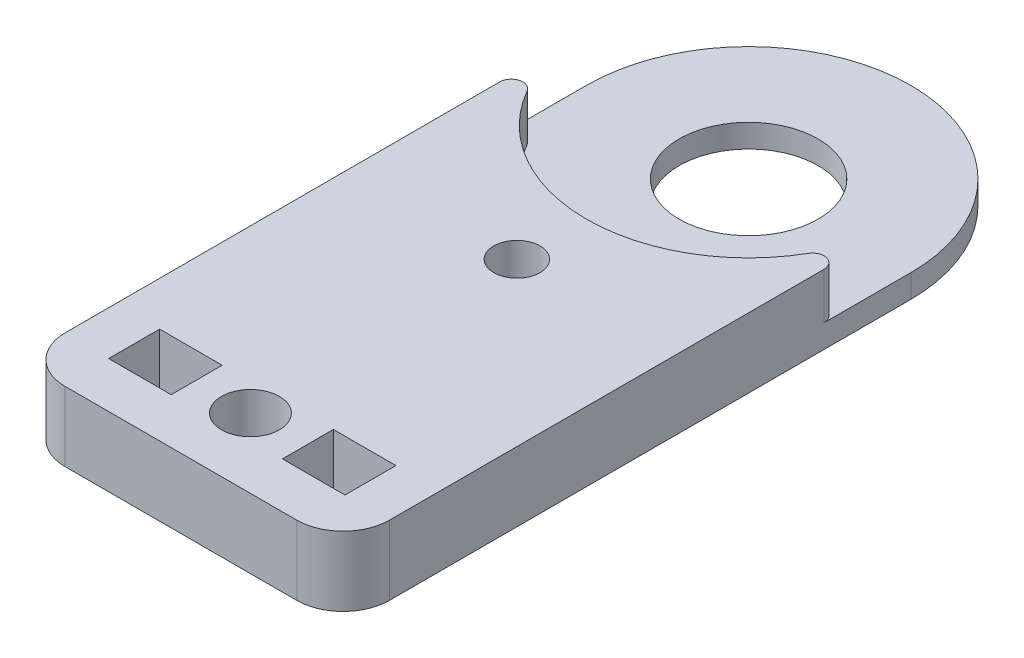
SolidWorks part; units mm, degrees
note: The reader was unsure of these and kept them because the rebuilt part matched: shared geometry of "草图1<4>".
ref_plane "前视基准面" through (0, 0, 0) normal (0, 0, 1) x (1, 0, 0)
ref_plane "上视基准面" through (0, 0, 0) normal (0, 1, 0) x (1, 0, 0)
ref_plane "右视基准面" through (0, 0, 0) normal (1, 0, 0) x (0, 0, -1)
sketch "草图1" plane through (0, 0, 0) normal (0, 1, 0) x (1, 0, 0)
  line L0 (0, 12.25) -> (0, 2.25)
  line L1 (-7, -12.25) -> (7, -12.25)
  line L2 (-7, -12.25) -> (-7, 12.25)
  line L3 (-7, 12.25) -> (7, 12.25)
  line L4 (7, -12.25) -> (7, 12.25)
  line L5 (-7, -12.25) -> (7, 12.25) construction
  line L6 (-7, 12.25) -> (7, -12.25) construction
  line L7 (0, 0) -> (0, -12.25) construction
  line L8 (-2.4, -8.0707) -> (-5.1, -8.0707)
  line L9 (-2.4, -8.0707) -> (-2.4, -10.2707)
  line L10 (-2.4, -10.2707) -> (-5.1, -10.2707)
  line L11 (-5.1, -8.0707) -> (-5.1, -10.2707)
  line L12 (-2.4, -8.0707) -> (-5.1, -10.2707) construction
  line L13 (-2.4, -10.2707) -> (-5.1, -8.0707) construction
  line L14 (2.4, -10.2707) -> (5.1, -8.0707) construction
  line L15 (2.4, -8.0707) -> (5.1, -10.2707) construction
  line L16 (5.1, -8.0707) -> (5.1, -10.2707)
  line L17 (2.4, -10.2707) -> (5.1, -10.2707)
  line L18 (2.4, -8.0707) -> (2.4, -10.2707)
  line L19 (2.4, -8.0707) -> (5.1, -8.0707)
  circle A0 centre (0, 12.25) radius 7
  circle A1 centre (0, 12.25) radius 3
  circle A2 centre (0, 2.25) radius 1
  circle A3 centre (0, -9.25) radius 1.25
  point P0 (0, 0)
  point P13 (-3.75, -9.1707)
  point P24 (3.75, -9.1707)
  dimension "D1" = 14
  dimension "D3" = 6
  dimension "D5" = 2
  dimension "D6" = 2.5
  dimension "D2" = 24.5
  dimension "D4" = 10
  dimension "D7" = 3
  dimension "D8" = 2.7
  dimension "D9" = 2.2
  dimension "D10" = 3.75
  dimension "D11" = 7
extrude "凸台-拉伸2" add sketch "草图1" along normal blind 1 contours A1 L3 A0 | A1 L3 A0 L0 | A1 L0 A0 L3
extrude "凸台-拉伸3" add sketch "草图1<4>" along normal blind 3
sketch "草图1<4>" plane through (0, 0, 0) normal (0, 1, 0) x (1, 0, 0) same geometry as "草图1"
fillet "圆角1" radius 0.5 2 edges at (7, 2, -12.25) (-7, 2, -12.25)
fillet "圆角2" radius 2 2 edges at (7, 1.5, 12.25) (-7, 1.5, 12.25)
